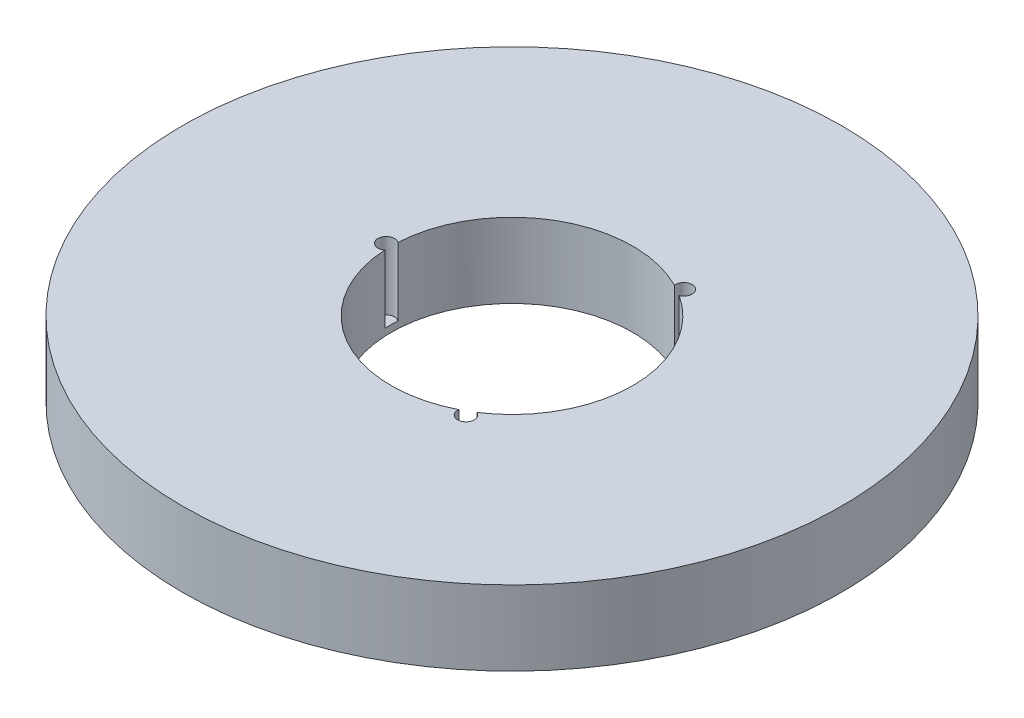
SolidWorks part; units mm, degrees
ref_plane "Front Plane" through (0, 0, 0) normal (0, 0, 1) x (1, 0, 0)
ref_plane "Top Plane" through (0, 0, 0) normal (0, 1, 0) x (1, 0, 0)
ref_plane "Right Plane" through (0, 0, 0) normal (1, 0, 0) x (0, 0, -1)
sketch "Sketch1" plane through (0, 0, 0) normal (0, 1, 0) x (1, 0, 0)
  circle A0 centre (0, 0) radius 75
  dimension "FLANGE_OD" = 150
extrude "Boss-Extrude1" add sketch "Sketch1" along normal blind 17
sketch "Sketch2" plane through (0, 0, 0) normal (0, 1, 0) x (1, 0, 0)
  circle A0 centre (0, 0) radius 27.5
  dimension "BORE_D" = 55
extrude "Cut-Extrude1" cut sketch "Sketch2" along normal through all
sketch "Sketch3" plane through (0, 17, 0) normal (0, 1, 0) x (1, 0, 0)
  circle A0 centre (0, 0) radius 28.6214 construction
  circle A1 centre (-28.6214, 0) radius 1.8954
  dimension "BOLT_D" = 3.7908
  dimension "BOLT_PCD" = 57.2427
extrude "Cut-Extrude2" cut sketch "Sketch3" against normal blind 15.4623
pattern_circular "CirPattern1" count 3 over 360 about axis through (0, 0, 0) along (0, 1, 0) of "Cut-Extrude2"
